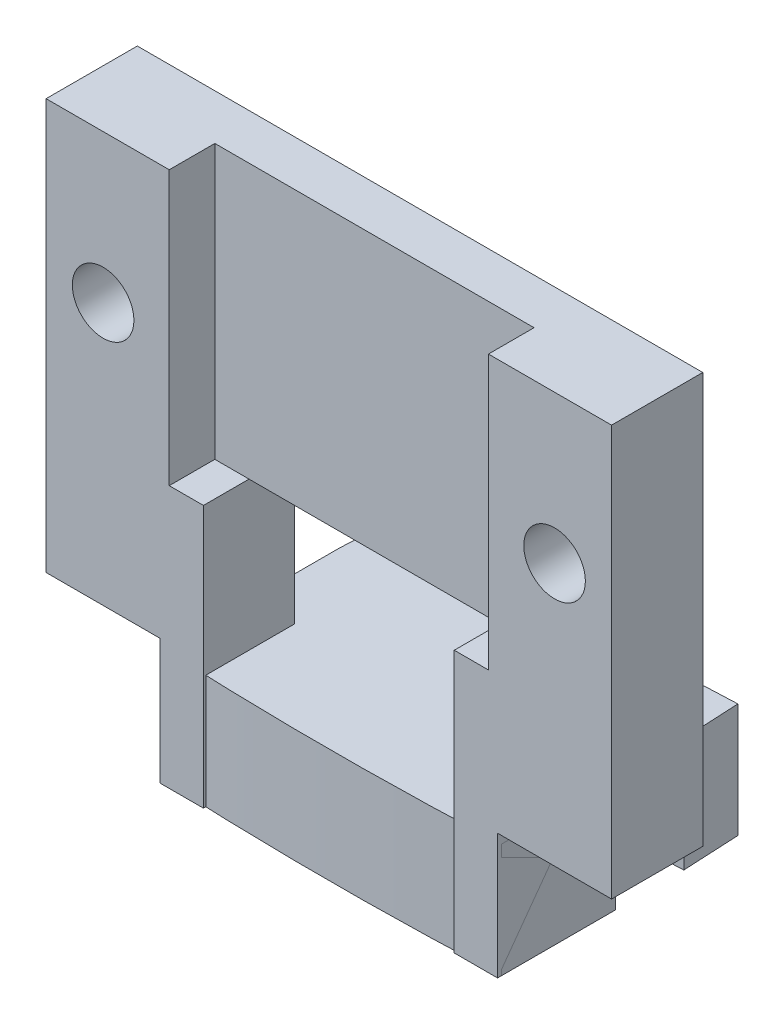
SolidWorks part; units mm, degrees
ref_plane "Front Plane" through (0, 0, 0) normal (0, 0, 1) x (1, 0, 0)
ref_plane "Top Plane" through (0, 0, 0) normal (0, 1, 0) x (1, 0, 0)
ref_plane "Right Plane" through (0, 0, 0) normal (1, 0, 0) x (0, 0, -1)
ref_axis "Axis2" through (0, 11, 0) along (0, -1, 0)
ref_plane "Plane2" through (0, 0, 154.5) normal (0, 0, 1) x (1, 0, 0)
sketch "Sketch7" plane through (0, 0, 154.5) normal (0, 0, 1) x (1, 0, 0)
  line L0 (-12.4, 0) -> (-5.5, 0)
  line L1 (-12.4, 23.5) -> (12.4, 23.5)
  line L2 (-12.4, 23.5) -> (-12.4, 0)
  line L3 (-5.5, 0) -> (-5.5, 11.5)
  line L4 (12.4, 23.5) -> (12.4, 0)
  line L5 (-5.5, 11.5) -> (5.5, 11.5)
  line L6 (5.5, 11.5) -> (5.5, 0)
  line L7 (5.5, 0) -> (12.4, 0)
  point P4 (0, -5)
  point P5 (14.3512, -0.3409)
  point P6 (12.4, 0)
  point P11 (0, 23.5)
  point P13 (-12.4, -11.75)
  point P14 (-12.4, 0.3248)
  dimension "D1" = 24.8
  dimension "D3" = 11
  dimension "D4" = 11.5
  dimension "D5" = 12
extrude "Main" add sketch "Sketch7" along normal mid plane 4
sketch "Sketch8" plane through (0, 0, 156.5) normal (0, 0, 1) x (1, 0, 0)
  line L0 (12.4, 23.5) -> (-12.4, 23.5) construction
  line L1 (-12.4, 23.5) -> (-12.4, 0) construction
  circle A0 centre (-9.9, 17) radius 1.35
  circle A1 centre (9.9, 17) radius 1.35
  dimension "D1" = 2.7
  dimension "D2" = 19.8
  dimension "D3" = 6.5
  dimension "D4" = 2.5
extrude "Holes" cut sketch "Sketch8" against normal through all
sketch "Sketch9" plane through (0, 0, 156.5) normal (0, 0, 1) x (1, 0, 0)
  line L1 (7, 23.5) -> (-7, 23.5)
  line L2 (7, 23.5) -> (7, 11.5)
  line L3 (7, 11.5) -> (-7, 11.5)
  line L4 (-7, 23.5) -> (-7, 11.5)
  line L5 (-12.4, 23.5) -> (-12.4, 0) construction
  line L6 (12.4, 23.5) -> (-12.4, 23.5) construction
  dimension "D1" = 5.4
  dimension "D2" = 14
  dimension "D3" = 12
extrude "ComponentHoles" cut sketch "Sketch9" against normal blind 2
sketch "Sketch10" plane through (0, 0, 0) normal (1, 0, 0) x (0, 0, -1)
  line L0 (-147.95, 3.1) -> (-152.05, 3.1)
  line L1 (-147.95, 3.1) -> (-148.5, 2.05)
  line L2 (-148.5, 2.05) -> (-148.5, 0)
  line L3 (-148.5, 0) -> (-146, 0)
  line L4 (-146, 0) -> (-146, 5)
  line L5 (-146, 5) -> (-156.5, 5)
  line L6 (-156.5, 5) -> (-156.5, 0)
  line L7 (-152.05, 3.1) -> (-151.5, 2.05)
  line L8 (-151.5, 2.05) -> (-151.5, 0)
  line L9 (-151.5, 0) -> (-156.5, 0)
  point P9 (-151.25, 5)
  point P12 (-150, 3.1)
  dimension "D1" = 3
  dimension "D2" = 5
  dimension "D3" = 4.1
  dimension "D4" = 2.05
  dimension "D5" = 3.1
  dimension "D6" = 5
  dimension "D7" = 150
  dimension "D8" = 5
  dimension "D9" = 2.5
revolve "Support" add sketch "Sketch10" angle 5.7 mid plane about axis through (0, 11, 0) along (0, -1, 0)
sketch "Sketch11" plane through (0, 0, 156.5) normal (0, 0, 1) x (1, 0, 0)
  line L0 (-12.4, 23.5) -> (-12.4, 0) construction
  line L1 (-12.4, 5.5) -> (-7.4, 5.5)
  line L2 (-12.4, 5.5) -> (-12.4, 0)
  line L3 (-12.4, 0) -> (-7.4, 0)
  line L4 (-7.4, 5.5) -> (-7.4, 0)
  line L5 (-12.4, 0) -> (-5.5, 0) construction
  line L6 (12.4, 0) -> (12.4, 23.5) construction
  line L7 (12.4, 5.5) -> (7.4, 5.5)
  line L8 (12.4, 5.5) -> (12.4, 0)
  line L9 (12.4, 0) -> (7.4, 0)
  line L10 (7.4, 5.5) -> (7.4, 0)
  line L11 (5.5, 0) -> (12.4, 0) construction
  dimension "D1" = 5
  dimension "D2" = 5.5
extrude "Support-Cut" cut sketch "Sketch11" against normal through all
